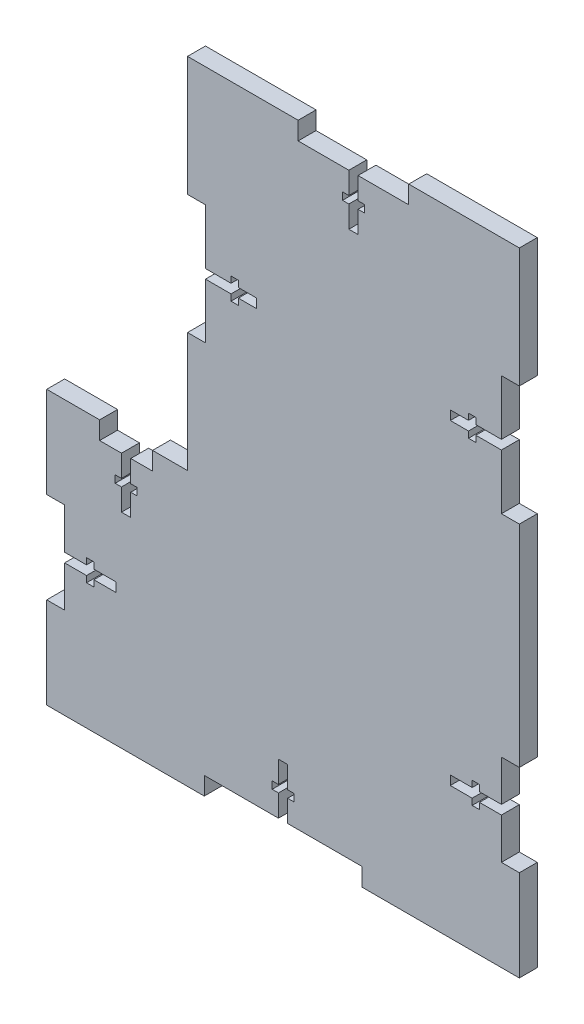
SolidWorks part; units mm, degrees
ref_plane "Front Plane" through (0, 0, 0) normal (0, 0, 1) x (1, 0, 0)
ref_plane "Top Plane" through (0, 0, 0) normal (0, 1, 0) x (1, 0, 0)
ref_plane "Right Plane" through (0, 0, 0) normal (1, 0, 0) x (0, 0, -1)
sketch "Sketch1" plane through (0, 0, 0) normal (0, 0, 1) x (1, 0, 0)
  line L1 (-66.929, -38.735) -> (66.929, -38.735)
  line L2 (-66.929, -38.735) -> (-66.929, 38.735)
  line L3 (-66.929, 38.735) -> (66.929, 38.735)
  line L4 (66.929, -38.735) -> (66.929, 38.735)
  line L5 (-66.929, -38.735) -> (66.929, 38.735) construction
  line L6 (-66.929, 38.735) -> (66.929, -38.735) construction
  point P0 (0, 0)
  dimension "D1" = 133.858
  dimension "D2" = 77.47
extrude "Boss-Extrude1" add sketch "Sketch1" along normal blind 5.08
sketch "Sketch2" plane through (0, 0, 5.08) normal (0, 0, 1) x (1, 0, 0)
  line L1 (-51.943, 38.735) -> (-36.957, 38.735)
  line L2 (-51.943, 38.735) -> (-51.943, 33.655)
  line L3 (-51.943, 33.655) -> (-36.957, 33.655)
  line L4 (-36.957, 38.735) -> (-36.957, 33.655)
  line L5 (66.929, 38.735) -> (-66.929, 38.735) construction
  line L6 (0, 0) -> (66.929, 0) construction
  line L7 (66.929, -38.735) -> (66.929, 38.735) construction
  dimension "D1" = 14.986
  dimension "D2" = 5.08
  dimension "D3" = 14.986
extrude "Cut-Extrude1" cut sketch "Sketch2" against normal through all
sketch "Sketch3" plane through (0, 0, 5.08) normal (0, 0, 1) x (1, 0, 0)
  line L0 (-66.929, 38.735) -> (-66.929, -38.735) construction
  line L1 (-66.929, 12.9117) -> (-61.849, 12.9117)
  line L2 (-66.929, 12.9117) -> (-66.929, -12.9117)
  line L3 (-66.929, -12.9117) -> (-61.849, -12.9117)
  line L4 (-61.849, 12.9117) -> (-61.849, -12.9117)
  line L5 (0, 0) -> (0, 39.951) construction
  line L6 (66.929, -12.9117) -> (61.849, -12.9117)
  line L7 (66.929, 12.9117) -> (66.929, -12.9117)
  line L8 (66.929, 12.9117) -> (61.849, 12.9117)
  line L9 (61.849, 12.9117) -> (61.849, -12.9117)
  dimension "D1" = 5.08
  dimension "D2" = 25.8233
  dimension "D3" = 25.8233
extrude "Cut-Extrude2" cut sketch "Sketch3" against normal through all
sketch "Sketch4" plane through (0, 0, 5.08) normal (0, 0, 1) x (1, 0, 0)
  line L0 (0, 0) -> (-61.849, 0) construction
  line L1 (-61.849, -12.9117) -> (-61.849, 12.9117) construction
  line L2 (0, 0) -> (0, 28.5152) construction
  line L3 (-61.849, 1.3017) -> (-47.371, 1.3017)
  line L4 (-61.849, 1.3017) -> (-61.849, -1.3018)
  line L5 (-61.849, -1.3018) -> (-47.371, -1.3018)
  line L6 (-47.371, 1.3017) -> (-47.371, -1.3018)
  line L7 (47.371, 1.3018) -> (47.371, -1.3018)
  line L8 (61.849, -1.3017) -> (47.371, -1.3018)
  line L9 (61.849, 1.3017) -> (61.849, -1.3017)
  line L10 (61.849, 1.3017) -> (47.371, 1.3018)
  line L11 (-66.929, -12.9117) -> (-66.929, 12.9117) construction
  point P9 (-47.371, 0)
  dimension "D1" = 1.3017
  dimension "D2" = 19.558
extrude "Cut-Extrude3" cut sketch "Sketch4" against normal through all
sketch "Sketch5" plane through (0, 0, 5.08) normal (0, 0, 1) x (1, 0, 0)
  line L0 (-44.45, 33.655) -> (-44.45, 4.7969) construction
  line L1 (-51.943, 33.655) -> (-36.957, 33.655) construction
  line L2 (0, 0) -> (35.9654, 0) construction
  line L3 (-43.1483, 33.655) -> (-45.7518, 33.655)
  line L4 (-43.1483, 33.655) -> (-43.1483, 19.177)
  line L5 (-43.1483, 19.177) -> (-45.7518, 19.177)
  line L6 (-45.7518, 33.655) -> (-45.7518, 19.177)
  point P11 (-44.45, 33.655)
  dimension "D1" = 2.6035
  dimension "D3" = 14.478
extrude "Cut-Extrude4" cut sketch "Sketch5" against normal through all
sketch "Sketch6" plane through (0, 0, 5.08) normal (0, 0, 1) x (1, 0, 0)
  line L0 (-54.61, 1.3017) -> (-54.61, -1.3018) construction
  line L1 (-47.371, 1.3017) -> (-61.849, 1.3017) construction
  line L2 (-61.849, -1.3018) -> (-47.371, -1.3018) construction
  line L3 (-43.1483, 26.416) -> (-45.7518, 26.416) construction
  line L4 (-43.1483, 33.655) -> (-43.1483, 19.177) construction
  line L5 (-45.7518, 19.177) -> (-45.7518, 33.655) construction
  line L6 (-43.1483, 26.416) -> (-47.5361, 26.416) construction
  line L7 (-47.5361, 27.4574) -> (-41.3639, 27.4574)
  line L8 (-47.5361, 27.4574) -> (-47.5361, 25.3746)
  line L9 (-47.5361, 25.3746) -> (-41.3639, 25.3746)
  line L10 (-41.3639, 27.4574) -> (-41.3639, 25.3746)
  line L11 (0, 0) -> (19.2929, 0) construction
  line L12 (0, 0) -> (0, 14.5303) construction
  line L17 (-54.61, -1.3018) -> (-54.61, -3.0861) construction
  line L18 (-55.6514, 3.0861) -> (-53.5686, 3.0861)
  line L19 (-55.6514, 3.0861) -> (-55.6514, -3.0861)
  line L20 (-55.6514, -3.0861) -> (-53.5686, -3.0861)
  line L21 (-53.5686, 3.0861) -> (-53.5686, -3.0861)
  line L22 (-44.45, 19.177) -> (-44.45, 25.3746) construction
  line L23 (-43.1483, 19.177) -> (-45.7518, 19.177) construction
  line L24 (-47.371, 0) -> (-53.5686, 0) construction
  line L25 (-47.371, -1.3018) -> (-47.371, 1.3017) construction
  line L26 (55.6514, -3.0861) -> (53.5686, -3.0861)
  line L27 (53.5686, 3.0861) -> (53.5686, -3.0861)
  line L28 (55.6514, 3.0861) -> (55.6514, -3.0861)
  line L29 (55.6514, 3.0861) -> (53.5686, 3.0861)
  dimension "D1" = 6.1722
  dimension "D2" = 2.0828
  dimension "D3" = 2.0828
  dimension "D4" = 6.1722
extrude "Cut-Extrude5" cut sketch "Sketch6" against normal through all
sketch "Sketch7" plane through (0, 0, 5.08) normal (0, 0, 1) x (1, 0, 0)
  line L0 (66.929, 38.735) -> (66.929, 140.335)
  line L1 (66.929, 140.335) -> (-27.051, 140.335)
  line L2 (-27.051, 140.335) -> (-27.051, 38.735)
  line L3 (66.929, 38.735) -> (-36.957, 38.735) construction
  line L60 (-43.1483, 27.4574) -> (-41.3639, 27.4574)
  line L61 (-41.3639, 27.4574) -> (-41.3639, 25.3746)
  line L62 (-41.3639, 25.3746) -> (-43.1483, 25.3746)
  line L63 (-43.1483, 19.177) -> (-45.7518, 19.177)
  line L64 (-45.7518, 25.3746) -> (-47.5361, 25.3746)
  line L65 (-47.5361, 25.3746) -> (-47.5361, 27.4574)
  line L66 (-47.5361, 27.4574) -> (-45.7518, 27.4574)
  line L67 (-45.7518, 33.655) -> (-51.943, 33.655)
  line L68 (-43.1483, 33.655) -> (-43.1483, 27.4574)
  line L70 (-43.1483, 25.3746) -> (-43.1483, 19.177)
  line L72 (61.849, -1.3018) -> (55.6514, -1.3018)
  line L73 (55.6514, -1.3018) -> (55.6514, -3.0861)
  line L74 (55.6514, -3.0861) -> (53.5686, -3.0861)
  line L75 (53.5686, -3.0861) -> (53.5686, -1.3017)
  line L76 (53.5686, -1.3017) -> (47.371, -1.3017)
  line L77 (47.371, -1.3017) -> (47.371, 1.3018)
  line L78 (47.371, 1.3018) -> (53.5686, 1.3018)
  line L79 (53.5686, 1.3018) -> (53.5686, 3.0861)
  line L80 (53.5686, 3.0861) -> (55.6514, 3.0861)
  line L81 (55.6514, 3.0861) -> (55.6514, 1.3018)
  line L82 (55.6514, 1.3018) -> (61.849, 1.3018)
  line L83 (61.849, 1.3018) -> (61.849, 12.9117)
  line L84 (61.849, 12.9117) -> (66.929, 12.9117)
  line L85 (66.929, 12.9117) -> (66.929, 38.735)
  line L86 (66.929, 38.735) -> (-36.957, 38.735)
  line L87 (-36.957, 38.735) -> (-36.957, 33.655)
  line L88 (-36.957, 33.655) -> (-43.1483, 33.655)
  line L89 (-45.7518, 19.177) -> (-45.7518, 25.3746)
  line L91 (-45.7518, 27.4574) -> (-45.7518, 33.655)
  line L101 (-51.943, 33.655) -> (-51.943, 38.735)
  line L102 (-51.943, 38.735) -> (-66.929, 38.735)
  line L103 (-66.929, 38.735) -> (-66.929, 12.9117)
  line L104 (-66.929, 12.9117) -> (-61.849, 12.9117)
  line L105 (-61.849, 12.9117) -> (-61.849, 1.3017)
  line L106 (-61.849, 1.3017) -> (-55.6514, 1.3017)
  line L107 (-55.6514, 1.3017) -> (-55.6514, 3.0861)
  line L108 (-55.6514, 3.0861) -> (-53.5686, 3.0861)
  line L109 (-53.5686, 3.0861) -> (-53.5686, 1.3017)
  line L110 (-53.5686, 1.3017) -> (-47.371, 1.3017)
  line L111 (-47.371, 1.3017) -> (-47.371, -1.3018)
  line L112 (-47.371, -1.3018) -> (-53.5686, -1.3018)
  line L113 (-53.5686, -1.3018) -> (-53.5686, -3.0861)
  line L114 (-53.5686, -3.0861) -> (-55.6514, -3.0861)
  line L115 (-55.6514, -3.0861) -> (-55.6514, -1.3018)
  line L116 (-55.6514, -1.3018) -> (-61.849, -1.3018)
  line L117 (-61.849, -1.3018) -> (-61.849, -12.9117)
  line L118 (-61.849, -12.9117) -> (-66.929, -12.9117)
  line L119 (-66.929, -12.9117) -> (-66.929, -38.735)
  line L120 (-66.929, -38.735) -> (66.929, -38.735)
  line L137 (66.929, -38.735) -> (66.929, -12.9117)
  line L138 (66.929, -12.9117) -> (61.849, -12.9117)
  line L139 (61.849, -12.9117) -> (61.849, -1.3018)
  line L154 (66.929, 38.735) -> (-27.051, 38.735)
  dimension "D1" = 101.6
  dimension "D2" = 93.98
  dimension "D3" = 0
extrude "Boss-Extrude2" add sketch "Sketch7" against normal blind 5.08
sketch "Sketch8" plane through (0, 0, 5.08) normal (0, 0, 1) x (1, 0, 0)
  line L0 (-66.929, -38.735) -> (66.929, -38.735) construction
  line L1 (22.3097, -38.735) -> (-22.3097, -38.735)
  line L2 (22.3097, -38.735) -> (22.3097, -33.655)
  line L3 (22.3097, -33.655) -> (-22.3097, -33.655)
  line L4 (-22.3097, -38.735) -> (-22.3097, -33.655)
  dimension "D1" = 5.08
  dimension "D2" = 44.6193
  dimension "D3" = 44.6193
extrude "Cut-Extrude6" cut sketch "Sketch8" against normal through all
sketch "Sketch10" plane through (0, 0, 5.08) normal (0, 0, 1) x (1, 0, 0)
  line L0 (22.3097, -33.655) -> (-22.3097, -33.655) construction
  line L1 (1.3018, -33.655) -> (-1.3018, -33.655)
  line L2 (1.3018, -33.655) -> (1.3017, -19.177)
  line L3 (1.3017, -19.177) -> (-1.3018, -19.177)
  line L4 (-1.3018, -33.655) -> (-1.3018, -19.177)
  line L5 (0, -19.177) -> (0, 0) construction
  dimension "D1" = 2.6035
  dimension "D2" = 14.478
extrude "Cut-Extrude7" cut sketch "Sketch10" against normal through all
sketch "Sketch11" plane through (0, 0, 5.08) normal (0, 0, 1) x (1, 0, 0)
  line L0 (3.0861, -26.416) -> (3.0861, -33.655) construction
  line L1 (22.3097, -33.655) -> (1.3018, -33.655) construction
  line L2 (-3.0861, -25.3746) -> (3.0861, -25.3746)
  line L3 (-3.0861, -25.3746) -> (-3.0861, -27.4574)
  line L4 (-3.0861, -27.4574) -> (3.0861, -27.4574)
  line L5 (3.0861, -25.3746) -> (3.0861, -27.4574)
  line L6 (-1.3018, -19.177) -> (-1.3017, -33.655) construction
  point P8 (-1.3017, -27.4574)
  dimension "D1" = 2.0828
  dimension "D2" = 6.1722
  dimension "D3" = 7.239
  dimension "D4" = 1.7844
extrude "Cut-Extrude8" cut sketch "Sketch11" against normal through all
sketch "Sketch12" plane through (0, 0, 5.08) normal (0, 0, 1) x (1, 0, 0)
  line L0 (66.929, 12.9117) -> (66.929, 140.335) construction
  line L1 (66.929, 72.6017) -> (61.849, 72.6017)
  line L2 (66.929, 72.6017) -> (66.929, 106.4683)
  line L3 (66.929, 106.4683) -> (61.849, 106.4683)
  line L4 (61.849, 72.6017) -> (61.849, 106.4683)
  line L5 (19.939, 140.335) -> (19.939, 42.6911) construction
  line L6 (66.929, 140.335) -> (-27.051, 140.335) construction
  line L7 (-21.971, 72.6017) -> (-21.971, 106.4683)
  line L8 (-27.051, 106.4683) -> (-21.971, 106.4683)
  line L9 (-27.051, 72.6017) -> (-27.051, 106.4683)
  line L10 (-27.051, 72.6017) -> (-21.971, 72.6017)
  dimension "D1" = 5.08
  dimension "D2" = 33.8667
  dimension "D3" = 33.8667
extrude "Cut-Extrude9" cut sketch "Sketch12" against normal through all
sketch "Sketch13" plane through (0, 0, 5.08) normal (0, 0, 1) x (1, 0, 0)
  line L0 (47.371, 89.535) -> (61.849, 89.535) construction
  line L1 (61.849, 106.4683) -> (61.849, 72.6017) construction
  line L2 (19.939, 140.335) -> (19.939, 63.8669) construction
  line L3 (66.929, 140.335) -> (-27.051, 140.335) construction
  line L4 (-21.971, 88.2332) -> (-21.971, 90.8367)
  line L5 (47.371, 88.2332) -> (61.849, 88.2332)
  line L6 (47.371, 88.2332) -> (47.371, 90.8367)
  line L7 (47.371, 90.8367) -> (61.849, 90.8367)
  line L8 (61.849, 88.2332) -> (61.849, 90.8367)
  line L9 (-7.493, 90.8367) -> (-21.971, 90.8367)
  line L10 (-7.493, 88.2332) -> (-7.493, 90.8367)
  line L11 (-7.493, 88.2332) -> (-21.971, 88.2332)
  line L12 (19.939, 130.1398) -> (19.939, 140.335) construction
  line L13 (21.2407, 140.335) -> (18.6373, 140.335)
  line L14 (21.2407, 140.335) -> (21.2408, 120.777)
  line L15 (21.2408, 120.777) -> (18.6373, 120.777)
  line L16 (18.6373, 140.335) -> (18.6373, 120.777)
  dimension "D1" = 2.6035
  dimension "D2" = 14.478
  dimension "D3" = 2.6035
  dimension "D4" = 19.558
extrude "Cut-Extrude10" cut sketch "Sketch13" against normal through all
sketch "Sketch14" plane through (0, 0, 5.08) normal (0, 0, 1) x (1, 0, 0)
  line L0 (54.61, 93.7894) -> (61.849, 93.7894) construction
  line L1 (54.61, 86.4489) -> (52.5272, 86.4489)
  line L2 (54.61, 86.4489) -> (54.61, 92.6211)
  line L3 (54.61, 92.6211) -> (52.5272, 92.6211)
  line L4 (52.5272, 86.4489) -> (52.5272, 92.6211)
  line L5 (61.849, 106.4683) -> (61.849, 90.8367) construction
  line L6 (61.849, 90.8367) -> (47.371, 90.8367) construction
  line L7 (19.939, 140.335) -> (19.939, -38.735) construction
  line L9 (-14.732, 92.6211) -> (-12.6492, 92.6211)
  line L10 (-14.732, 86.4489) -> (-14.732, 92.6211)
  line L11 (-12.6492, 86.4489) -> (-12.6492, 92.6211)
  line L12 (-14.732, 86.4489) -> (-12.6492, 86.4489)
  line L14 (21.2407, 140.335) -> (18.6373, 140.335) construction
  line L15 (18.6373, 140.335) -> (18.6373, 120.777) construction
  line L16 (23.0251, 126.9746) -> (16.8529, 126.9746)
  line L17 (23.0251, 126.9746) -> (23.0251, 129.0574)
  line L18 (23.0251, 129.0574) -> (16.8529, 129.0574)
  line L19 (16.8529, 126.9746) -> (16.8529, 129.0574)
  line L20 (16.8529, 128.016) -> (16.8529, 140.335) construction
  line L21 (18.6373, 140.335) -> (-27.051, 140.335) construction
  point P8 (52.5272, 90.8367)
  point P25 (18.6373, 126.9746)
  dimension "D1" = 2.0828
  dimension "D2" = 6.1722
  dimension "D3" = 7.239
  dimension "D4" = 1.7844
  dimension "D5" = 2.0828
  dimension "D6" = 6.1722
  dimension "D7" = 1.7844
  dimension "D8" = 12.319
extrude "Cut-Extrude11" cut sketch "Sketch14" against normal through all
sketch "Sketch15" plane through (0, 0, 5.08) normal (0, 0, 1) x (1, 0, 0)
  line L0 (66.929, 140.335) -> (21.2407, 140.335) construction
  line L1 (35.6023, 140.335) -> (4.2757, 140.335)
  line L2 (35.6023, 140.335) -> (35.6023, 135.255)
  line L3 (35.6023, 135.255) -> (4.2757, 135.255)
  line L4 (4.2757, 140.335) -> (4.2757, 135.255)
  dimension "D1" = 5.08
  dimension "D2" = 31.3267
  dimension "D3" = 31.3267
extrude "Cut-Extrude12" cut sketch "Sketch15" against normal through all
equation "\"Length\"= \"Length@Box.SLDASM\""
equation "\"D1@Sketch1\"  = \"Length\" + 2 * \"Material\""
equation "\"Width\"= \"Short Height@Box.SLDASM\""
equation "\"D2@Sketch1\" = \"Width\" + 2 * \"Material\""
equation "\"Material\"= \"Material@Box.SLDASM\""
equation "\"D1@Boss-Extrude1\" = \"Material\""
equation "\"D1@Sketch2\"=(\"Length\" -\"Over Hang@Box.SLDASM\"+\"Material\"*2)/3"
equation "\"D2@Sketch2\"= \"Material\""
equation "\"D3@Sketch2\"=(\"Length\" -\"Over Hang@Box.SLDASM\"+\"Material\"*2)/3"
equation "\"D1@Sketch3\"=\"Material\""
equation "\"D2@Sketch3\"=(\"Width\" +\"Material\"*2)/3"
equation "\"D3@Sketch3\"=(\"Width\" +\"Material\"*2)/3"
equation "\"Diameter of Screw\"= \"Diameter of Screw@Box.SLDASM\""
equation "\"Length of screw\"= \"Length of Screw@Box.SLDASM\""
equation "\"D3@Sketch5\"= \"Length of screw\" - \"Material\""
equation "\"D1@Sketch5\" = \"Diameter of Screw\""
equation "\"D1@Sketch4\"= \"Diameter of Screw\" /2"
equation "\"D2@Sketch4\"=\"Length of screw\""
equation "\"Diameter of Nut\"= \"Diameter of Nut@Box.SLDASM\""
equation "\"D1@Sketch6\"=\"Diameter of Nut\""
equation "\"Height of Nut\"= \"Height of Nut@Box.SLDASM\""
equation "\"D3@Sketch6\"= \"Height of Nut\""
equation "\"D4@Sketch6\"=\"Diameter of Nut\""
equation "\"D2@Sketch6\"=\"Height of Nut\""
equation "\"D1@Sketch7\"= \"Long Height@Box.SLDASM\"-\"Short Height@Box.SLDASM\""
equation "\"D2@Sketch7\" = \"Over Hang@Box.SLDASM\" + \"Material\""
equation "\"D1@Boss-Extrude2\" = \"Material\""
equation "\"D1@Sketch8\"= \"Material\""
equation "\"D2@Sketch8\"=(\"Length\" + \"Material\"*2)/3"
equation "\"D3@Sketch8\"=(\"Length\" + \"Material\"*2)/3"
equation "\"D1@Sketch10\"=\"Diameter of Screw\""
equation "\"D2@Sketch10\"=\"Length of screw\" - \"Material\""
equation "\"D3@Sketch11\" = ( \"Length of screw\" - \"Material\" ) / 2"
equation "\"D4@Sketch11\"= ( \"Diameter of Nut\"-\"Diameter of Screw\" )/2"
equation "\"D1@Sketch12\"=\"Material\""
equation "\"D2@Sketch12\"=(\"Long Height@Box.SLDASM\"-\"Short Height@Box.SLDASM\")/3"
equation "\"D3@Sketch12\"=(\"Long Height@Box.SLDASM\"-\"Short Height@Box.SLDASM\")/3"
equation "\"D1@Sketch13\"=\"Diameter of Screw\""
equation "\"D2@Sketch13\"=\"Length of screw\"-\"Material\""
equation "\"D1@Sketch14\"=\"Height of Nut\""
equation "\"D2@Sketch14\"=\"Diameter of Nut\""
equation "\"D3@Sketch14\"=(\"Length of screw\"-\"Material\")/2"
equation "\"D4@Sketch14\"=(\"Diameter of Nut\"-\"Diameter of Screw\")/2"
equation "\"D1@Sketch15\"= \"Material\""
equation "\"D2@Sketch15\"=(\"Material\"+ \"over hang@Box.SLDASM\" )/3"
equation "\"D3@Sketch15\"=(\"Material\" + \"over hang@Box.SLDASM\" )/3"
equation "\"D3@Sketch13\"=\"Diameter of Screw\""
equation "\"D4@Sketch13\"=\"Length of screw\""
equation "\"D5@Sketch14\"=\"Height of Nut\""
equation "\"D6@Sketch14\"=\"Diameter of Nut\""
equation "\"D7@Sketch14\"=(\"Diameter of Nut\"-\"Diameter of Screw\")/2"
equation "\"D8@Sketch14\"=(\"Length of screw\"-\"Material\")/2 + \"Material\""
